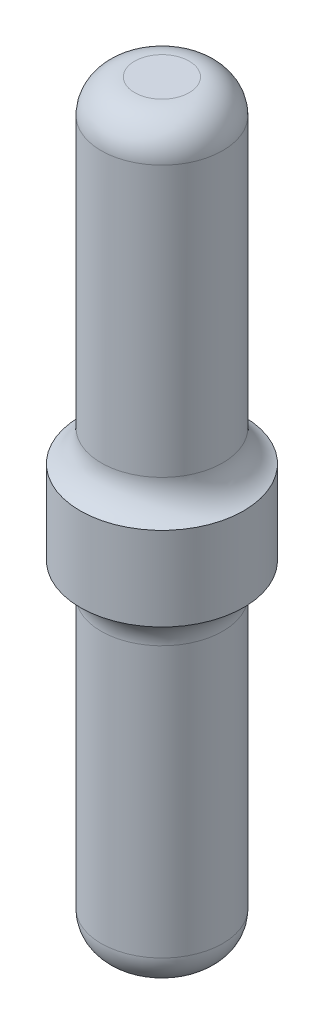
SolidWorks part; units mm, degrees
ref_plane "Alzado" through (0, 0, 0) normal (0, 0, 1) x (1, 0, 0)
ref_plane "Planta" through (0, 0, 0) normal (0, 1, 0) x (1, 0, 0)
ref_plane "Vista lateral" through (0, 0, 0) normal (1, 0, 0) x (0, 0, -1)
sketch "Croquis1" plane through (0, 0, 0) normal (0, 1, 0) x (1, 0, 0)
  circle A0 centre (0, 0) radius 2.44
  dimension "D1" = 4.88
extrude "Saliente-Extruir1" add sketch "Croquis1" along normal blind 2.5
sketch "Croquis2" plane through (0, 2.5, 0) normal (0, 1, 0) x (1, 0, 0)
  circle A0 centre (0, 0) radius 1.815
  dimension "D1" = 3.63
sketch "Croquis3" plane through (0, 0, 0) normal (0, -1, 0) x (1, 0, 0)
  circle A0 centre (0, 0) radius 1.815 construction
  circle A1 centre (0, 0) radius 1.815
extrude "Saliente-Extruir2" add sketch "Croquis2" along normal blind 10
extrude "Saliente-Extruir3" add sketch "Croquis3" along normal blind 10
fillet "Redondeo1" radius 1 2 edges at (0, 0, -1.815) (0, 2.5, 1.815)
fillet "Redondeo2" radius 1 2 edges at (0, 12.5, 1.815) (0, -10, -1.815)
